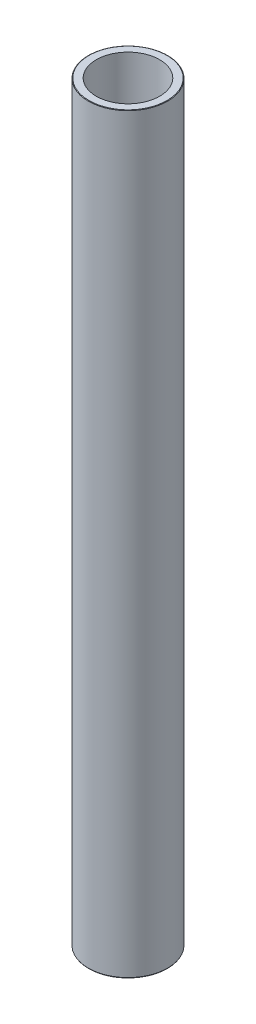
SolidWorks part; units mm, degrees
ref_plane "Front Plane" through (0, 0, 0) normal (0, 0, 1) x (1, 0, 0)
ref_plane "Top Plane" through (0, 0, 0) normal (0, 1, 0) x (1, 0, 0)
ref_plane "Right Plane" through (0, 0, 0) normal (1, 0, 0) x (0, 0, -1)
sketch "Sketch1" plane through (0, 0, 0) normal (0, 1, 0) x (1, 0, 0)
  circle A0 centre (0, 0) radius 30
  dimension "SHAFT_OD" = 60
extrude "Boss-Extrude1" add sketch "Sketch1" along normal blind 569.1525
sketch "Sketch2" plane through (0, 0, 0) normal (0, 1, 0) x (1, 0, 0)
  circle A0 centre (0, 0) radius 24.0075
  dimension "BORE_D" = 48.015
extrude "Cut-Extrude1" cut sketch "Sketch2" along normal through all
chamfer "Chamfer1" distance 0.254 angle 60 2 edges at (0, 569.1525, 30) (0, 0, 30) first distance on face at (0, 569.1525, 30) first distance on face at (0, 0, 24.0075)
